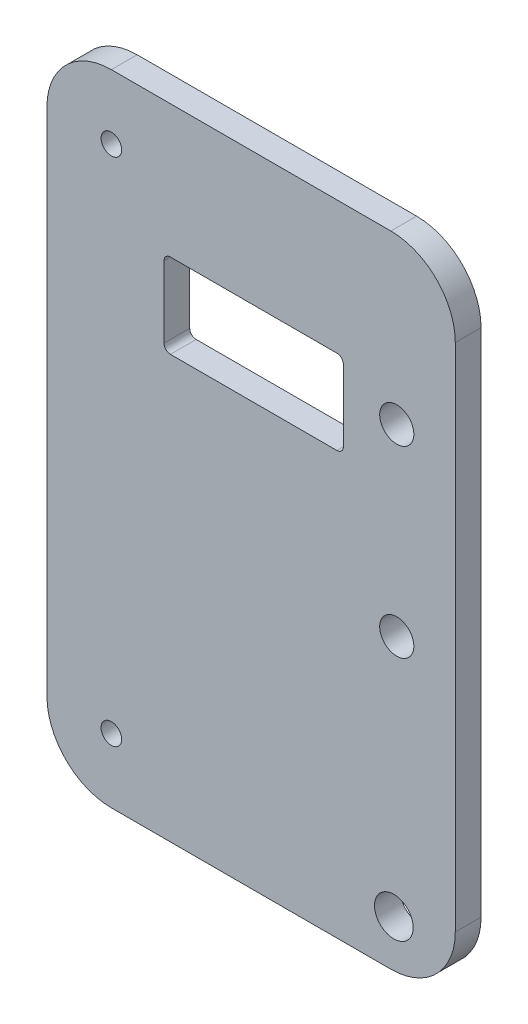
SolidWorks part; units mm, degrees
ref_plane "Front Plane" through (0, 0, 0) normal (0, 0, 1) x (1, 0, 0)
ref_plane "Top Plane" through (0, 0, 0) normal (0, 1, 0) x (1, 0, 0)
ref_plane "Right Plane" through (0, 0, 0) normal (1, 0, 0) x (0, 0, -1)
sketch "Sketch1" plane through (0, 0, 0) normal (0, 0, 1) x (1, 0, 0)
  line L1 (-108.4636, -267.8694) -> (-45.0794, -267.8694)
  line L2 (-108.4636, -267.8694) -> (-108.4636, -367.109)
  line L3 (-108.4636, -367.109) -> (-45.0794, -367.109)
  line L4 (-45.0794, -267.8694) -> (-45.0794, -367.109)
  line L5 (-63.4534, -301.5579) -> (-89.2971, -301.5579)
  line L6 (-62.4534, -300.5579) -> (-62.4534, -289.4797)
  line L7 (-63.4534, -288.4797) -> (-89.2971, -288.4797)
  line L8 (-90.2971, -300.5579) -> (-90.2971, -289.4797)
  arc A0 (-89.2971, -301.5579) -> (-90.2971, -300.5579) centre (-89.2971, -300.5579) cw
  arc A1 (-89.2971, -288.4797) -> (-90.2971, -289.4797) centre (-89.2971, -289.4797) ccw
  arc A2 (-62.4534, -289.4797) -> (-63.4534, -288.4797) centre (-63.4534, -289.4797) ccw
  arc A3 (-63.4534, -301.5579) -> (-62.4534, -300.5579) centre (-63.4534, -300.5579) ccw
  dimension "D1" = 1
extrude "Boss-Extrude1" add sketch "Sketch1" along normal blind 4
hole_wizard "M5 Clearance Hole1" positions "Sketch4" profile "Sketch2" hole size "M5" standard "ISO" end condition through all
sketch "Sketch4" plane through (0, 0, 4) normal (0, 0, 1) x (1, 0, 0)
  point P0 (-54.1627, -321.9157)
  point P2 (-54.1627, -293.4157)
sketch "Sketch2" plane through (-54.1627, -321.9157, 4) normal (1, 0, 0) x (0, -1, 0)
  line L0 (0, 0) -> (0, 4)
  line L1 (0, 4) -> (2.65, 4)
  line L2 (2.65, 4) -> (2.65, 0)
  line L5 (2.65, 0) -> (0, 0)
  line L11 (0, -6.35) -> (0, 107.95) construction
  dimension "Thru Hole Dia." = 5.3
  dimension "Thru Hole Depth" = 4
fillet "Fillet1" radius 10 4 edges at (-108.4636, -267.8694, 2) (-45.0794, -267.8694, 2) (-108.4636, -367.109, 2) (-45.0794, -367.109, 2)
hole_wizard "M5 Clearance Hole2" positions "Sketch6" profile "Sketch5" hole size "M5" standard "ISO" end condition through all
sketch "Sketch6" plane through (0, 0, 0) normal (0, 0, -1) x (-1, 0, 0)
  line L24 (-96.2636, -309.6657) -> (-96.2636, -364.3029) construction
  line L25 (-92.2636, -368.3029) -> (59.1173, -368.3029) construction
  line L26 (63.1173, -364.3029) -> (63.1173, -309.6657) construction
  line L27 (59.1173, -305.6657) -> (55.1173, -305.6657) construction
  line L28 (51.1173, -301.6657) -> (51.1173, -289.4157) construction
  line L29 (47.1173, -285.4157) -> (-80.2636, -285.4157) construction
  line L30 (-84.2636, -289.4157) -> (-84.2636, -301.6657) construction
  line L31 (-88.2636, -305.6657) -> (-92.2636, -305.6657) construction
  arc A24 (-96.2636, -364.3029) -> (-92.2636, -368.3029) centre (-92.2636, -364.3029) ccw construction
  arc A25 (59.1173, -368.3029) -> (63.1173, -364.3029) centre (59.1173, -364.3029) ccw construction
  arc A26 (63.1173, -309.6657) -> (59.1173, -305.6657) centre (59.1173, -309.6657) ccw construction
  arc A27 (51.1173, -301.6657) -> (55.1173, -305.6657) centre (55.1173, -301.6657) ccw construction
  arc A28 (51.1173, -289.4157) -> (47.1173, -285.4157) centre (47.1173, -289.4157) ccw construction
  arc A29 (-80.2636, -285.4157) -> (-84.2636, -289.4157) centre (-80.2636, -289.4157) ccw construction
  arc A30 (-88.2636, -305.6657) -> (-84.2636, -301.6657) centre (-88.2636, -301.6657) ccw construction
  arc A31 (-92.2636, -305.6657) -> (-96.2636, -309.6657) centre (-92.2636, -309.6657) ccw construction
  point P0 (54.6173, -359.8029)
  dimension "D1" = 8.5
  dimension "D2" = 8.5
sketch "Sketch5" plane through (-54.6173, -359.8029, 0) normal (1, 0, 0) x (0, 1, 0)
  line L0 (0, 0) -> (0, 4)
  line L1 (0, 4) -> (3, 4)
  line L2 (3, 4) -> (3, 0)
  line L5 (3, 0) -> (0, 0)
  line L11 (0, -6.35) -> (0, 107.95) construction
  dimension "Thru Hole Dia." = 6
  dimension "Thru Hole Depth" = 4
sketch "Sketch7" plane through (0, 0, 4) normal (0, 0, 1) x (1, 0, 0)
  line L0 (-108.4636, -277.8694) -> (-108.4636, -357.109) construction
  line L1 (-108.4636, -333.6557) -> (-105.4252, -333.6557)
  line L2 (-108.4636, -333.6557) -> (-108.4636, -305.6397)
  line L3 (-79.3727, -256.1535) -> (-105.4252, -256.1535)
  line L4 (-105.4252, -333.6557) -> (-105.4252, -256.1535)
  line L7 (-108.4636, -305.6397) -> (-79.3727, -305.6397)
  line L8 (-79.3727, -256.1535) -> (-79.3727, -305.6397)
extrude "Boss-Extrude2" [suppressed] add sketch "Sketch7" against normal up to surface (4 mm away) up to face at (-57.6173, -359.8029, 0)
sketch "Sketch8" [suppressed] plane through (0, 0, 0) normal (0, 0, -1) x (-1, 0, 0)
  line L0 (79.3727, -305.6397) -> (63.2759, -305.6397) construction
  line L1 (71.3243, -251.637) -> (23.8623, -251.637)
  line L2 (71.3243, -251.637) -> (71.3243, -305.6397)
  line L3 (71.3243, -305.6397) -> (23.8623, -305.6397)
  line L4 (23.8623, -251.637) -> (23.8623, -305.6397)
extrude "Cut-Extrude1" [suppressed] cut sketch "Sketch8" against normal blind 14.4
fillet "Fillet2" [suppressed] radius 8
hole_wizard "M3 Clearance Hole1" positions "Sketch10" profile "Sketch9" hole size "M3" standard "ISO" end condition through all
sketch "Sketch10" plane through (0, 0, 4) normal (0, 0, 1) x (1, 0, 0)
  point P0 (-98.4636, -357.109)
  point P3 (-98.4636, -277.8694)
sketch "Sketch9" plane through (-98.4636, -357.109, 4) normal (1, 0, 0) x (0, -1, 0)
  line L0 (0, 0) -> (0, 4)
  line L1 (0, 4) -> (1.6, 4)
  line L2 (1.6, 4) -> (1.6, 0)
  line L5 (1.6, 0) -> (0, 0)
  line L11 (0, -6.35) -> (0, 107.95) construction
  dimension "Thru Hole Dia." = 3.2
  dimension "Thru Hole Depth" = 4
